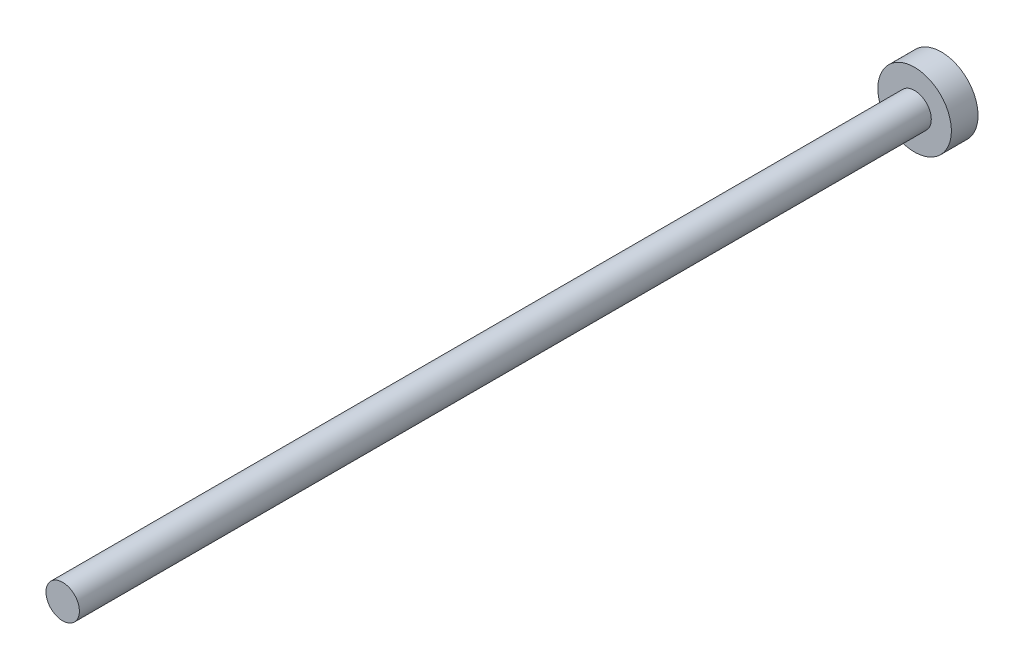
SolidWorks part; units mm, degrees
material "ABS"
ref_plane "Front Plane" through (0, 0, 0) normal (0, 0, 1) x (1, 0, 0)
ref_plane "Top Plane" through (0, 0, 0) normal (0, 1, 0) x (1, 0, 0)
ref_plane "Right Plane" through (0, 0, 0) normal (1, 0, 0) x (0, 0, -1)
sketch "Sketch1" plane through (0, 0, 0) normal (0, 0, 1) x (1, 0, 0)
  circle A0 centre (0, 0) radius 2.5
  dimension "D1" = 5
extrude "Boss-Extrude1" add sketch "Sketch1" along normal mid plane 127.5
sketch "Sketch2" plane through (0, 0, -63.75) normal (0, 0, -1) x (-1, 0, 0)
  circle A0 centre (0, 0) radius 5.5
  circle A1 centre (0, 0) radius 2.5 construction
  dimension "D1" = 3
extrude "Boss-Extrude2" add sketch "Sketch2" along normal blind 4
